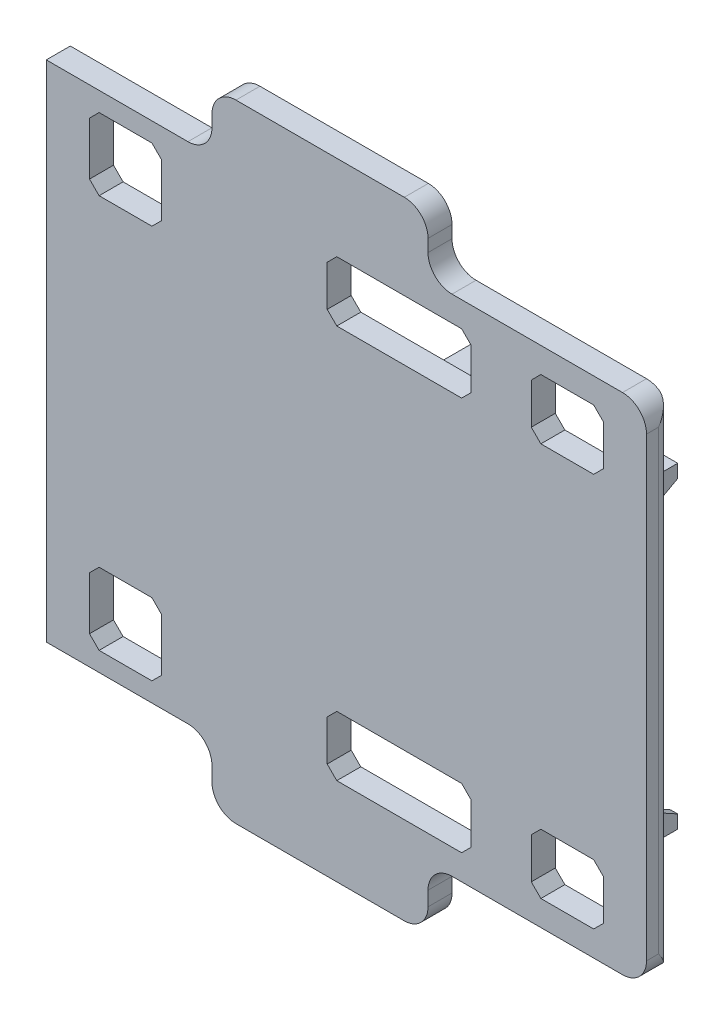
SolidWorks part; units mm, degrees
ref_plane "前视基准面" through (0, 0, 0) normal (0, 0, 1) x (1, 0, 0)
ref_plane "上视基准面" through (0, 0, 0) normal (0, 1, 0) x (1, 0, 0)
ref_plane "右视基准面" through (0, 0, 0) normal (1, 0, 0) x (0, 0, -1)
sketch "草图1" plane through (0, 0, 0) normal (0, 0, 1) x (1, 0, 0)
  line L0 (-45, 115) -> (-45, 120)
  line L1 (-114, 105) -> (-55, 105)
  line L2 (-114, 95) -> (-114, -95)
  line L3 (-114, -105) -> (-55, -105)
  line L4 (136, 95) -> (136, -95)
  line L5 (-114, 95) -> (-114, 105)
  line L7 (-35, 130) -> (35.1247, 130)
  line L8 (45, 120.1247) -> (45, 115)
  line L9 (-45, -115) -> (-45, -121.0101)
  line L10 (-35, -131.0101) -> (35, -131.0101)
  line L11 (45, -121.0101) -> (45, -115)
  line L12 (55, 105) -> (126, 105)
  line L13 (55, -105) -> (115, -105)
  line L15 (132.8114, 102.3216) -> (136, 105) construction
  line L16 (-159.0816, 0) -> (162.8742, 0) construction
  line L17 (0, -160.1649) -> (0, 164.862) construction
  line L18 (-114, -95) -> (-114, -105)
  line L22 (126, -105) -> (115, -105)
  arc A2 (136, 95) -> (126, 105) centre (126, 95) ccw
  arc A4 (-55, 105) -> (-45, 115) centre (-55, 115) ccw
  arc A5 (55, 105) -> (45, 115) centre (55, 115) cw
  arc A6 (-35, 130) -> (-45, 120) centre (-35, 120) ccw
  arc A7 (45, 120.1247) -> (35.1247, 130) centre (35.1247, 120.1247) ccw
  arc A8 (-45, -115) -> (-55, -105) centre (-55, -115) ccw
  arc A9 (45, -115) -> (55, -105) centre (55, -115) cw
  arc A10 (-35, -131.0101) -> (-45, -121.0101) centre (-35, -121.0101) cw
  arc A11 (35, -131.0101) -> (45, -121.0101) centre (35, -121.0101) ccw
  arc A13 (126, -105) -> (136, -95) centre (126, -95) ccw
  point P0 (0, 0)
  point P28 (-45.35, 105)
  point P32 (45, 105)
  point P40 (45, -105)
  dimension "D2" = 45
  dimension "D3" = 10
  dimension "D4" = 45
  dimension "D5" = 10
  dimension "D6" = 10
  dimension "D9" = 10
  dimension "D11" = 9.8753
  dimension "D7" = 10
  dimension "D8" = 10
  dimension "D10" = 10
  dimension "D12" = 10
  dimension "D13" = 210
  dimension "D14" = 59
  dimension "D15" = 59
extrude "凸台-拉伸1" add sketch "草图1" along normal blind 10
sketch "草图2" plane through (0, 0, 10) normal (0, 0, 1) x (1, 0, 0)
  line L0 (136, -95) -> (136, 95) construction
  line L1 (-96, 97) -> (-66, 97)
  line L2 (-96, 97) -> (-96, 67)
  line L3 (-96, 67) -> (-66, 67)
  line L4 (-66, 97) -> (-66, 67)
  line L5 (-96, 97) -> (-66, 67) construction
  line L6 (-96, 67) -> (-66, 97) construction
  line L7 (-96, -67) -> (-66, -67)
  line L8 (-96, -67) -> (-96, -97)
  line L9 (-96, -97) -> (-66, -97)
  line L10 (-66, -67) -> (-66, -97)
  line L11 (-96, -67) -> (-66, -97) construction
  line L12 (-96, -97) -> (-66, -67) construction
  line L13 (88, 94.5) -> (118, 94.5)
  line L14 (88, 94.5) -> (88, 69.5)
  line L15 (88, 69.5) -> (118, 69.5)
  line L16 (118, 94.5) -> (118, 69.5)
  line L17 (88, 94.5) -> (118, 69.5) construction
  line L18 (88, 69.5) -> (118, 94.5) construction
  line L19 (88, -69.5) -> (118, -69.5)
  line L20 (88, -69.5) -> (88, -94.5)
  line L21 (88, -94.5) -> (118, -94.5)
  line L22 (118, -69.5) -> (118, -94.5)
  line L23 (88, -69.5) -> (118, -94.5) construction
  line L24 (88, -94.5) -> (118, -69.5) construction
  line L25 (3, 94.5) -> (63, 94.5)
  line L26 (3, 94.5) -> (3, 69.5)
  line L27 (3, 69.5) -> (63, 69.5)
  line L28 (63, 94.5) -> (63, 69.5)
  line L29 (3, 94.5) -> (63, 69.5) construction
  line L30 (3, 69.5) -> (63, 94.5) construction
  line L31 (3, -69.5) -> (63, -69.5)
  line L32 (3, -69.5) -> (3, -94.5)
  line L33 (3, -94.5) -> (63, -94.5)
  line L34 (63, -69.5) -> (63, -94.5)
  line L35 (3, -69.5) -> (63, -94.5) construction
  line L36 (3, -94.5) -> (63, -69.5) construction
  line L37 (-55, 105) -> (-114, 105) construction
  line L38 (-114, -105) -> (-55, -105) construction
  line L39 (-114, 105) -> (-114, -105) construction
  point P0 (-81, 82)
  point P5 (-81, -82)
  point P10 (103, 82)
  point P15 (103, -82)
  point P20 (33, 82)
  point P25 (33, -82)
  dimension "D1" = 8
  dimension "D2" = 8
  dimension "D3" = 18
  dimension "D4" = 18
  dimension "D5" = 30
  dimension "D6" = 30
  dimension "D7" = 18
  dimension "D8" = 18
  dimension "D9" = 25
  dimension "D10" = 30
  dimension "D11" = 60
  dimension "D12" = 60
  dimension "D13" = 25
  dimension "D14" = 30
  dimension "D15" = 30
  dimension "D16" = 25
  dimension "D17" = 25
  dimension "D18" = 25
  dimension "D19" = 25
extrude "切除-拉伸1" cut sketch "草图2" against normal through all
fillet "圆角2" radius 5 1 edges at (136, 0, 0) tangent propagation no
chamfer "倒角1" distance 4 angle 45 24 edges at (-96, 67, 5) (-96, -97, 5) (3, -94.5, 5) (3, 69.5, 5) (88, -94.5, 5) (-96, 97, 5) (-96, -67, 5) (3, -69.5, 5) (88, -69.5, 5) (3, 94.5, 5) (-66, -97, 5) (-66, 67, 5) (63, -94.5, 5) (118, -94.5, 5) (63, 69.5, 5) (-66, -67, 5) (118, -69.5, 5) (63, -69.5, 5) (-66, 97, 5) (63, 94.5, 5) (88, 69.5, 5) (88, 94.5, 5) (118, 69.5, 5) (118, 94.5, 5)
sketch "草图12" plane through (0, 0, 0) normal (0, 0, -1) x (-1, 0, 0)
  line L0 (-124, 66) -> (-124, 55)
  line L1 (-124, 55) -> (-121, 55)
  line L2 (-121, 55) -> (-121, 63)
  line L3 (-121, 63) -> (-113, 63)
  line L4 (-113, 63) -> (-113, 66)
  line L5 (-113, 66) -> (-124, 66)
  line L6 (-160.4167, 0) -> (138.1475, 0) construction
  line L7 (-49, 63) -> (-41, 63)
  line L8 (-41, 63) -> (-41, 55)
  line L9 (-41, 55) -> (-38, 55)
  line L10 (-38, 55) -> (-38, 66)
  line L11 (-38, 66) -> (-49, 66)
  line L12 (-49, 66) -> (-49, 63)
  line L14 (-136, -95) -> (-136, 95) construction
  line L15 (-49, -66) -> (-49, -63)
  line L16 (-38, -66) -> (-49, -66)
  line L17 (-38, -55) -> (-38, -66)
  line L18 (-41, -55) -> (-38, -55)
  line L19 (-41, -63) -> (-41, -55)
  line L20 (-49, -63) -> (-41, -63)
  line L21 (-113, -66) -> (-124, -66)
  line L22 (-113, -63) -> (-113, -66)
  line L23 (-121, -63) -> (-113, -63)
  line L24 (-121, -55) -> (-121, -63)
  line L25 (-124, -55) -> (-121, -55)
  line L26 (-124, -66) -> (-124, -55)
  dimension "D1" = 3
  dimension "D2" = 3
  dimension "D3" = 3
  dimension "D4" = 3
  dimension "D5" = 80
  dimension "D6" = 12
  dimension "D7" = 63
  dimension "D8" = 8
extrude "凸台-拉伸3" add sketch "草图12" along normal blind 15
sketch "草图13" plane through (124, 0, 0) normal (1, 0, 0) x (0, 0, -1)
  line L0 (15, 60.5) -> (5, 55)
  line L1 (15, 66) -> (15, 55) construction
  line L2 (15, 55) -> (0, 55) construction
  line L3 (5, 55) -> (15, 55)
  line L4 (15, 55) -> (15, 60.5)
  line L5 (15, -60.5) -> (15, -55)
  line L6 (15, -55) -> (15, -66) construction
  line L7 (15, -55) -> (5, -55)
  line L8 (15, -55) -> (0, -55) construction
  line L9 (5, -55) -> (15, -60.5)
  dimension "D1" = 10
  dimension "D2" = 10
extrude "切除-拉伸9" cut sketch "草图13" against normal blind 3
sketch "草图14" plane through (0, -66, 0) normal (0, -1, 0) x (1, 0, 0)
  line L0 (118.5, -15) -> (113, -15)
  line L1 (124, -15) -> (113, -15) construction
  line L2 (113, -15) -> (113, -5)
  line L3 (113, -15) -> (113, 0) construction
  line L4 (113, -5) -> (118.5, -15)
  line L5 (43.5, -15) -> (49, -15)
  line L6 (49, -15) -> (38, -15) construction
  line L7 (49, -15) -> (49, 0) construction
  line L8 (49, -15) -> (49, -5)
  line L9 (49, -5) -> (43.5, -15)
  dimension "D1" = 10
  dimension "D2" = 10
extrude "切除-拉伸10" cut sketch "草图14" against normal blind 3
sketch "草图15" plane through (38, 0, 0) normal (-1, 0, 0) x (0, 0, 1)
  line L0 (-15, -60.5) -> (-15, -55)
  line L1 (-15, -66) -> (-15, -55) construction
  line L2 (-15, -55) -> (-5, -55)
  line L3 (-15, -55) -> (0, -55) construction
  line L4 (-5, -55) -> (-15, -60.5)
  line L5 (-15, 55) -> (-5, 55)
  line L6 (-15, 55) -> (0, 55) construction
  line L7 (-5, 55) -> (-15, 60.5)
  line L8 (-15, 55) -> (-15, 66) construction
  line L9 (-15, 60.5) -> (-15, 55)
  dimension "D1" = 10
  dimension "D2" = 10
extrude "切除-拉伸11" cut sketch "草图15" against normal blind 3
sketch "草图16" plane through (0, 66, 0) normal (0, 1, 0) x (1, 0, 0)
  line L0 (43.5, 15) -> (49, 15)
  line L1 (49, 15) -> (49, 5)
  line L2 (49, 5) -> (43.5, 15)
  line L3 (118.5, 15) -> (113, 15)
  line L4 (113, 15) -> (113, 5)
  line L5 (113, 15) -> (113, 0) construction
  line L6 (113, 5) -> (118.5, 15)
extrude "切除-拉伸12" cut sketch "草图16" against normal blind 3
chamfer "倒角2" distance 2 angle 45 8 edges at (43.5, -66, 0) (38, -60.5, 0) (124, -60.5, 0) (118.5, -66, 0) (124, 60.5, 0) (118.5, 66, 0) (38, 60.5, 0) (43.5, 66, 0)
equation "\"45、\"=43.7672"
